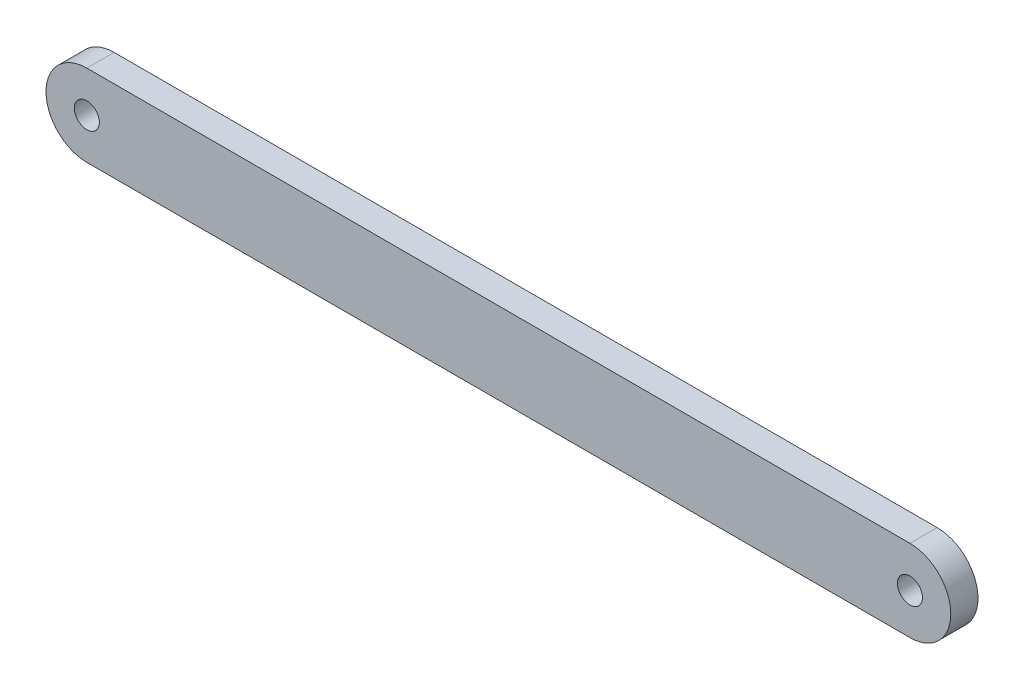
SolidWorks part; units mm, degrees
ref_plane "前视基准面" through (0, 0, 0) normal (0, 0, 1) x (1, 0, 0)
ref_plane "上视基准面" through (0, 0, 0) normal (0, 1, 0) x (1, 0, 0)
ref_plane "右视基准面" through (0, 0, 0) normal (1, 0, 0) x (0, 0, -1)
other "Configuration Table"
sketch "草图1" plane through (0, 0, 0) normal (0, 0, 1) x (1, 0, 0)
  line L1 (-75.6, 7.5) -> (75.6, 7.5)
  line L3 (-75.6, -7.5) -> (75.6, -7.5)
  line L5 (-75.6, 7.5) -> (75.6, -7.5) construction
  line L6 (-75.6, -7.5) -> (75.6, 7.5) construction
  arc A0 (-75.6, 7.5) -> (-75.6, -7.5) centre (-75.6, 0) ccw
  arc A1 (75.6, 7.5) -> (75.6, -7.5) centre (75.6, 0) cw
  circle A2 centre (-75.6, 0) radius 2.3
  circle A3 centre (75.6, 0) radius 2.3
  point P0 (0, 0)
  dimension "D1" = 4.6
  dimension "D2" = 4.6
  dimension "D3" = 151.2
  dimension "D4" = 15
extrude "凸台-拉伸1" add sketch "草图1" along normal blind 5
equation "\"fi\"=4.6"
equation "\"D1@草图1\"=\"fi\""
equation "\"D2@草图1\"=\"fi\""
equation "\"b0\"= 75.6'ground"
equation "\"D3@草图1\"=\"b4\""
equation "\"width\"=15"
equation "\"D4@草图1\"=\"width\""
equation "\"depth\"=5"
equation "\"D1@凸台-拉伸1\"=\"depth\""
equation "\"b1\"= \"b0\" *1.4/ 2'rocker"
equation "\"b2\"= \"b0\"'coupler"
equation "\"b3\"= \"b0\" / 2'coupler"
equation "\"b4\"= \"b0\" *2'leg"
equation "\"angle\"= 40*pi/180'ground水平夹角"
equation "\"b5\"=(\"b2\"^2+\"b4\"^2)^0.5'斜边"
